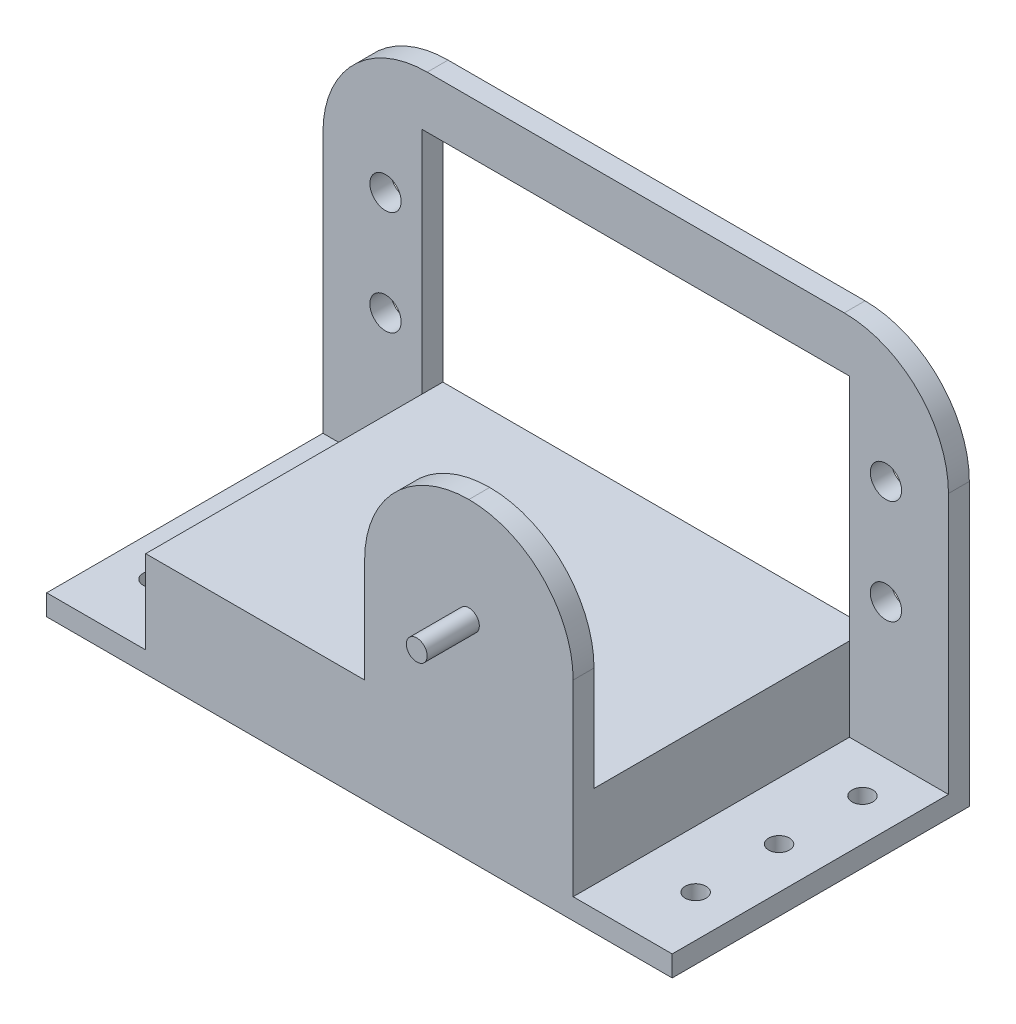
SolidWorks part; units mm, degrees
ref_plane "Front Plane" through (0, 0, 0) normal (0, 0, 1) x (1, 0, 0)
ref_plane "Top Plane" through (0, 0, 0) normal (0, 1, 0) x (1, 0, 0)
ref_plane "Right Plane" through (0, 0, 0) normal (1, 0, 0) x (0, 0, -1)
sketch "Sketch1" plane through (0, 0, 0) normal (0, 1, 0) x (1, 0, 0)
  line L1 (-30, 14.25) -> (30, 14.25)
  line L2 (-30, 14.25) -> (-30, -14.25)
  line L3 (-30, -14.25) -> (30, -14.25)
  line L4 (30, 14.25) -> (30, -14.25)
  line L5 (-30, 14.25) -> (30, -14.25) construction
  line L6 (-30, -14.25) -> (30, 14.25) construction
  point P0 (0, 0)
  dimension "D1" = 28.5
  dimension "D2" = 60
extrude "Boss-Extrude1" add sketch "Sketch1" along normal blind 2
sketch "Sketch2" plane through (0, 2, 0) normal (0, 1, 0) x (1, 0, 0)
  line L1 (-30, 14.25) -> (30, 14.25)
  line L2 (-30, 14.25) -> (-30, 12.25)
  line L3 (-30, 12.25) -> (30, 12.25)
  line L4 (30, 14.25) -> (30, 12.25)
  line L5 (-30, 14.25) -> (30, 12.25) construction
  line L6 (-30, 12.25) -> (30, 14.25) construction
  line L7 (30, -14.25) -> (30, 14.25) construction
  point P4 (0, 13.25)
  dimension "D1" = 2
  dimension "D2" = 60
extrude "Boss-Extrude2" add sketch "Sketch2" along normal blind 35
sketch "Sketch3" plane through (0, 2, 0) normal (0, 1, 0) x (1, 0, 0)
  line L0 (-30, -14.25) -> (30, -14.25) construction
  line L1 (-20.5, 14.25) -> (20.5, 14.25)
  line L2 (-20.5, 14.25) -> (-20.5, -14.25)
  line L3 (-20.5, -14.25) -> (20.5, -14.25)
  line L4 (20.5, 14.25) -> (20.5, -14.25)
  line L5 (-20.5, 14.25) -> (20.5, -14.25) construction
  line L6 (-20.5, -14.25) -> (20.5, 14.25) construction
  line L7 (-30, 12.25) -> (-30, -14.25) construction
  point P4 (0, 0)
  dimension "D1" = 28.5
  dimension "D2" = 41
  dimension "D3" = 9.5
extrude "Boss-Extrude3" add sketch "Sketch3" along normal blind 8
sketch "Sketch4" plane through (0, 10, 0) normal (0, 1, 0) x (1, 0, 0)
  line L1 (20.5, -14.25) -> (0.5, -14.25)
  line L2 (20.5, -14.25) -> (20.5, -12.25)
  line L3 (20.5, -12.25) -> (0.5, -12.25)
  line L4 (0.5, -14.25) -> (0.5, -12.25)
  line L5 (20.5, -14.25) -> (0.5, -12.25) construction
  line L6 (20.5, -12.25) -> (0.5, -14.25) construction
  point P4 (10.5, -13.25)
  dimension "D1" = 2
  dimension "D2" = 20
extrude "Boss-Extrude4" add sketch "Sketch4" along normal blind 20
sketch "Sketch5" plane through (0, 0, -14.25) normal (0, 0, -1) x (-1, 0, 0)
  line L1 (-20.5, 10) -> (20.5, 10)
  line L2 (-20.5, 10) -> (-20.5, 32)
  line L3 (-20.5, 32) -> (20.5, 32)
  line L4 (20.5, 10) -> (20.5, 32)
  line L5 (-20.5, 10) -> (20.5, 32) construction
  line L6 (-20.5, 32) -> (20.5, 10) construction
  line L7 (30, 37) -> (30, 0) construction
  line L8 (-30, 0) -> (30, 0) construction
  point P4 (0, 21)
  dimension "D1" = 22
  dimension "D2" = 41
  dimension "D3" = 9.5
  dimension "D4" = 10
extrude "Cut-Extrude1" cut sketch "Sketch5" against normal up to surface (2 mm away) up to face at (0, 12.75, -12.25)
sketch "Sketch6" plane through (0, 0, -14.25) normal (0, 0, -1) x (-1, 0, 0)
  line L0 (-35.8953, 22) -> (45.8703, 22) construction
  line L1 (-35.8953, 20) -> (36.6988, 20) construction
  line L2 (-20.5, 10) -> (20.5, 10) construction
  line L3 (20.5, 32) -> (-20.5, 32) construction
  line L4 (-20.5, 32) -> (-20.5, 10) construction
  circle A0 centre (-24, 25) radius 1.5
  circle A1 centre (-24, 15) radius 1.5
  dimension "D2" = 3
  dimension "D1" = 10
  dimension "D3" = 5
  dimension "D4" = 3.5
  dimension "D5" = 10
extrude "Cut-Extrude2" cut sketch "Sketch6" against normal up to surface (2 mm away) up to face at (0, 16.6, -12.25)
mirror "Mirror1" about plane through (0, 0, 0) normal (1, 0, 0) of "Cut-Extrude2"
sketch "Sketch7" plane through (0, 0, 14.25) normal (0, 0, 1) x (1, 0, 0)
  line L0 (20.5, 30) -> (20.5, 2) construction
  line L1 (-20.5, 10) -> (0.5, 10) construction
  circle A0 centre (10.5, 20) radius 1
  dimension "D1" = 2
  dimension "D2" = 10
  dimension "D3" = 10
extrude "Boss-Extrude5" add sketch "Sketch7" along normal blind 5
fillet "Fillet1" radius 10 2 edges at (0.5, 30, 13.25) (20.5, 30, 13.25)
fillet "Fillet2" radius 10 2 edges at (-30, 37, -13.25) (30, 37, -13.25)
sketch "Sketch8" plane through (0, 2, 0) normal (0, 1, 0) x (1, 0, 0)
  line L0 (-32.6568, 0) -> (32.3299, 0) construction
  circle A0 centre (-26, 0) radius 1
  circle A1 centre (-26, 8) radius 1
  circle A2 centre (-26, -8) radius 1
  point P9 (0, 0)
  dimension "D1" = 2
  dimension "D2" = 2
  dimension "D3" = 8
  dimension "D4" = 26
  dimension "D5" = 26
extrude "Cut-Extrude3" cut sketch "Sketch8" against normal up to surface (2 mm away) up to face at (0, 0, 0)
mirror "Mirror2" about plane through (0, 0, 0) normal (1, 0, 0) of "Cut-Extrude3"
